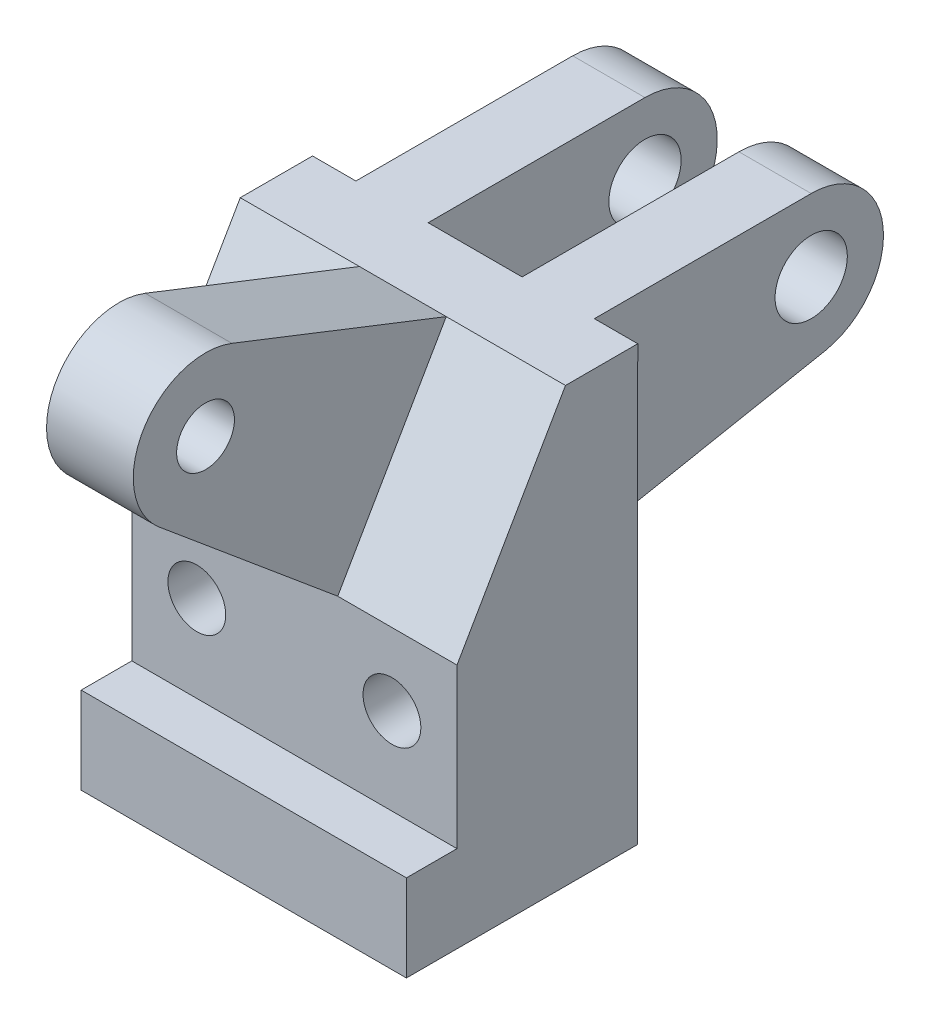
SolidWorks part; units mm, degrees
material "Hexcel AS4C (3000 Filaments)"
ref_plane "Front Plane" through (0, 0, 0) normal (0, 0, 1) x (1, 0, 0)
ref_plane "Top Plane" through (0, 0, 0) normal (0, 1, 0) x (1, 0, 0)
ref_plane "Right Plane" through (0, 0, 0) normal (1, 0, 0) x (0, 0, -1)
sketch "Sketch1" plane through (0, 0, 0) normal (1, 0, 0) x (0, 0, -1)
  line L0 (-16, 0.0192) -> (16, 0.0192)
  line L2 (-16, 12.0192) -> (-9, 12.0192)
  line L3 (-9, 12.0192) -> (-9, 34.0192)
  line L4 (-9, 34.0192) -> (6.0111, 60.0192)
  line L5 (6.0111, 60.0192) -> (16.0111, 60.0192)
  line L6 (16.0111, 60.0192) -> (16, 0.0192)
  line L7 (-16, 0.0192) -> (-16, 12.0192)
  dimension "D1" = 7
  dimension "D2" = 22
  dimension "D3" = 30
  dimension "D4" = 32
  dimension "D5" = 60
  dimension "D6" = 10
  dimension "D7" = 12
extrude "Boss-Extrude1" add sketch "Sketch1" along normal mid plane 45
sketch "Sketch2" plane through (0, 0, 0) normal (1, 0, 0) x (0, 0, -1)
  line L0 (16, 0.0192) -> (16.0111, 60.0192) construction
  line L1 (16.0063, 34.0192) -> (16.0111, 60.0192)
  line L2 (16.0111, 60.0192) -> (46.0111, 60.0192)
  line L3 (47.9134, 40.2018) -> (16.0063, 34.0192)
  arc A0 (47.9134, 40.2018) -> (46.0111, 60.0192) centre (46.0111, 50.0192) ccw
  circle A1 centre (46.0111, 50.0192) radius 5
  dimension "D2" = 20
  dimension "D4" = 10
  dimension "D1" = 30
  dimension "D3" = 26
extrude "Boss-Extrude2" add sketch "Sketch2" along normal blind 10 from offset 6.5
extrude "Boss-Extrude3" add sketch "Sketch2<2>" against normal blind 10 from offset 6.5 offset against normal yes
sketch "Sketch2<2>" plane through (0, 0, 0) normal (1, 0, 0) x (0, 0, -1) same geometry as "Sketch2"
sketch "Sketch3" plane through (0, 0, 0) normal (1, 0, 0) x (0, 0, -1)
  line L0 (6.0111, 60.0192) -> (-9, 34.0192) construction
  line L1 (6.0111, 60.0192) -> (-9, 34.0192)
  line L2 (-27.2934, 62.3341) -> (-1.4944, 47.0192) construction
  line L3 (6.0111, 60.0192) -> (-23.6437, 71.6443)
  line L4 (-9, 34.0192) -> (-33.705, 54.6601)
  arc A0 (-23.6437, 71.6443) -> (-33.705, 54.6601) centre (-27.2934, 62.3341) ccw
  circle A1 centre (-27.2934, 62.3341) radius 4
  dimension "D2" = 20
  dimension "D3" = 8
  dimension "D1" = 30
extrude "Boss-Extrude4" add sketch "Sketch3" along normal mid plane 12
sketch "Sketch4" plane through (0, 0, 9) normal (0, 0, 1) x (1, 0, 0)
  line L1 (22.5, 12.0192) -> (-22.5, 12.0192) construction
  line L2 (-22.5, 34.0192) -> (-22.5, 12.0192) construction
  circle A0 centre (-13.5, 24.0192) radius 4
  circle A1 centre (13.5, 24.0192) radius 4
  point P6 (0, 0)
  point P9 (0, 0)
  dimension "D1" = 8
  dimension "D2" = 9
  dimension "D3" = 27
  dimension "D4" = 12
extrude "Cut-Extrude1" cut sketch "Sketch4" against normal through all
